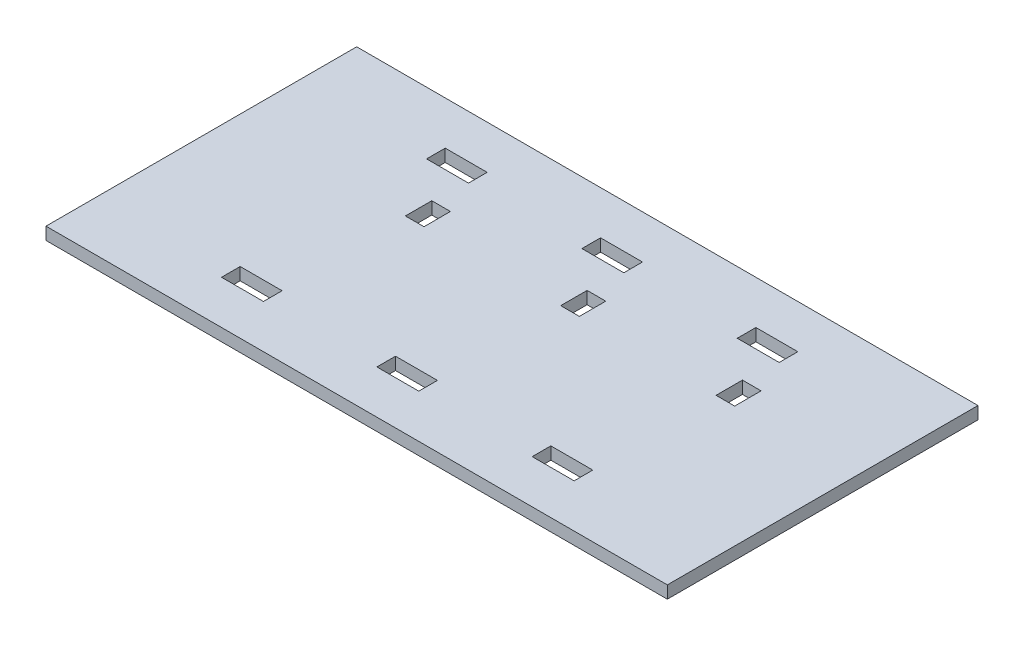
SolidWorks part; units mm, degrees
ref_plane "Front Plane" through (0, 0, 0) normal (0, 0, 1) x (1, 0, 0)
ref_plane "Top Plane" through (0, 0, 0) normal (0, 1, 0) x (1, 0, 0)
ref_plane "Right Plane" through (0, 0, 0) normal (1, 0, 0) x (0, 0, -1)
sketch "Sketch1" plane through (0, 0, 0) normal (0, 1, 0) x (1, 0, 0)
  line L1 (-50.8, -25.4) -> (50.8, -25.4)
  line L2 (-50.8, -25.4) -> (-50.8, 25.4)
  line L3 (-50.8, 25.4) -> (50.8, 25.4)
  line L4 (50.8, -25.4) -> (50.8, 25.4)
  line L5 (0, 25.4) -> (0, -25.4) construction
  line L6 (-50.8, 0) -> (50.8, 0) construction
  point P0 (0, 0)
  dimension "D1" = 50.8
  dimension "D2" = 101.6
extrude "Boss-Extrude1" add sketch "Sketch1" along normal blind 2.032
sketch "Sketch2" plane through (0, 2.032, 0) normal (0, 1, 0) x (1, 0, 0)
  line L0 (2.54, 5.425) -> (5.588, 5.425)
  line L1 (2.54, 5.425) -> (2.54, 9.743)
  line L2 (5.588, 5.425) -> (5.588, 9.743)
  line L3 (2.54, 9.743) -> (5.588, 9.743)
  circle A0 centre (4.064, 0) radius 5.635 construction
  point P3 (0, 0)
  point P6 (0, 0)
  point P9 (0, 0)
  point P10 (0, 0)
  point P11 (0, 0)
  point P12 (2.3345, 0)
  dimension "D1" = 11.27
  dimension "D2" = 4.064
  dimension "D3" = 3.048
  dimension "D4" = 4.318
extrude "Wire Hole" cut sketch "Sketch2" against normal through all contours L3 L1 L0 L2 region at (4.064, 2.032, -7.584)
sketch "Sketch3" plane through (0, 2.032, 0) normal (0, 1, 0) x (1, 0, 0)
  line L0 (-3.81, 15.24) -> (3.048, 15.24)
  line L1 (-3.81, 15.24) -> (-3.81, 18.288)
  line L2 (3.048, 15.24) -> (3.048, 18.288)
  line L3 (-3.81, 18.288) -> (3.048, 18.288)
  line L4 (-1.1176, 0) -> (1.1176, 0) construction
  dimension "D1" = 3.048
  dimension "D2" = 6.858
  dimension "D3" = 3.048
  dimension "D4" = 15.24
extrude "Cut-Extrude2" cut sketch "Sketch3" against normal through all
mirror "Mirror1" about plane through (0, 0, 0) normal (0, 0, 1) of "Cut-Extrude2"
pattern_linear "LPattern1" count 2 spacing 25.4 along (-1, 0, 0) count 2 spacing 25.4 along (1, 0, 0) of "Wire Hole", "Cut-Extrude2", "Mirror1"
equation "\"Arrow Height\"= 1in"
equation "\"Button Height\"= 2in"
equation "\"Button Width\"= 4in"
equation "\"Haptic Diameter\"= 10mm"
equation "\"Haptic Thickness\"= 2.7mm"
equation "\"D1@Sketch1\"=\"Button Height\""
equation "\"D2@Sketch1\"=\"Button Width\""
equation "\"Arrow Spacing\"= 1in"
equation "\"Arrow Width\"= 0.75in"
equation "\"Haptic Wire Angle\"= 63.43"
equation "\"Haptic Wire Width\"= .1in"
equation "\"Hatic Wire Height\"= .15in"
equation "\"D1@Sketch2\"=\"Haptic Diameter\"+.05"
equation "\"D3@Sketch2\"=\"Haptic Wire Width\"+.02"
equation "\"D4@Sketch2\"=\"Hatic Wire Height\"+.02"
